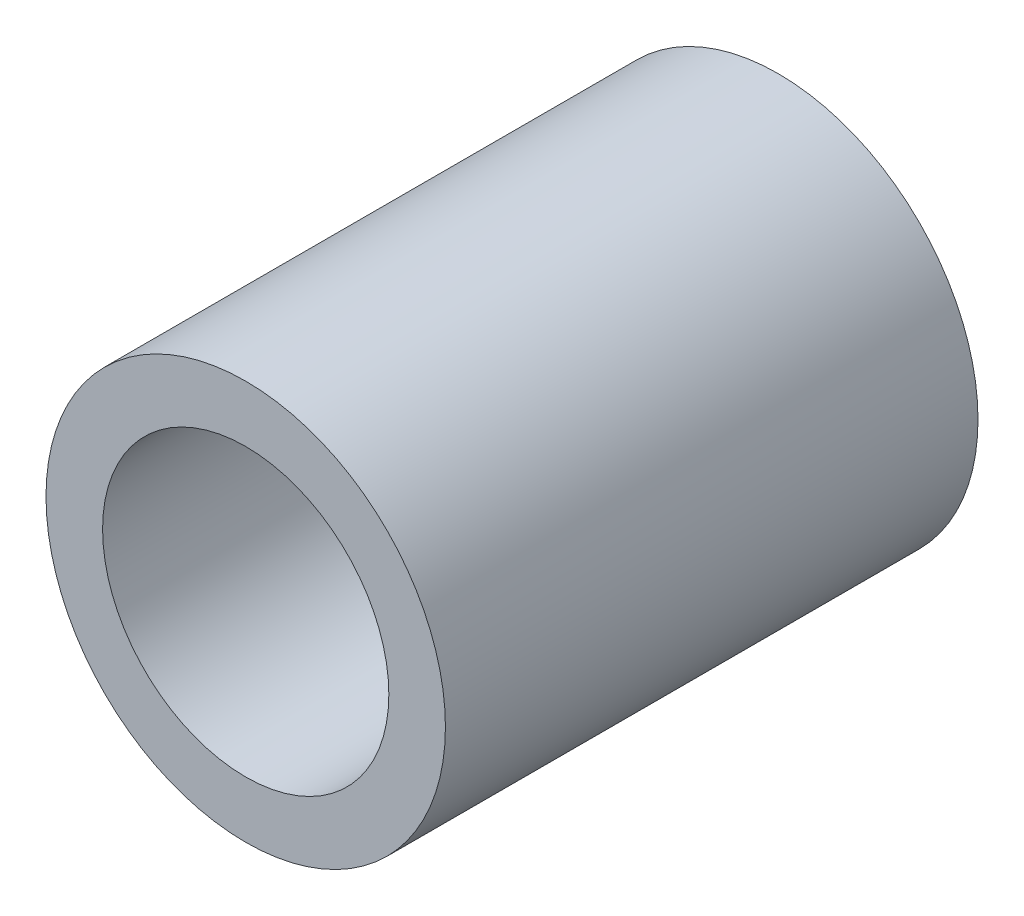
SolidWorks part; units mm, degrees
ref_plane "Front Plane" through (0, 0, 0) normal (0, 0, 1) x (1, 0, 0)
ref_plane "Top Plane" through (0, 0, 0) normal (0, 1, 0) x (1, 0, 0)
ref_plane "Right Plane" through (0, 0, 0) normal (1, 0, 0) x (0, 0, -1)
sketch "Sketch3" plane through (0, 0, 0) normal (0, 0, 1) x (1, 0, 0)
  circle A0 centre (0, 0) radius 2.15 construction
  circle A1 centre (0, 0) radius 3 construction
  point P6 (0, -2.15)
  dimension "OD" = 6
  dimension "ID" = 4.3
sketch "Sketch1" plane through (0, 0, 0) normal (1, 0, 0) x (0, 0, -1)
  line L0 (-4, -2.15) -> (-4, 2.15) construction
  line L1 (4, -3) -> (-4, -3) construction
  line L2 (4, -3) -> (4, 3) construction
  line L3 (4, 3) -> (-4, 3) construction
  line L4 (-4, -3) -> (-4, 3) construction
  line L5 (0, 3) -> (0, -3) construction
  line L6 (4, 0) -> (-4, 0) construction
  point P0 (0, 0)
  point P7 (-4, 0)
  dimension "OD" = 6
  dimension "ID" = 4.3
sketch "Sketch2" plane through (0, 0, 0) normal (0, 0, 1) x (1, 0, 0)
  circle A0 centre (0, 0) radius 3
  circle A1 centre (0, 0) radius 2.15
extrude "Extrude1" add sketch "Sketch2" along normal up to vertex and the other way up to vertex up to point (0, -3, 4) other way up to point (0, 3, -4)
equation "\"ID@Sketch1\" = \"ID@Sketch3\""
equation "\"OD@Sketch1\" = \"OD@Sketch3\""
